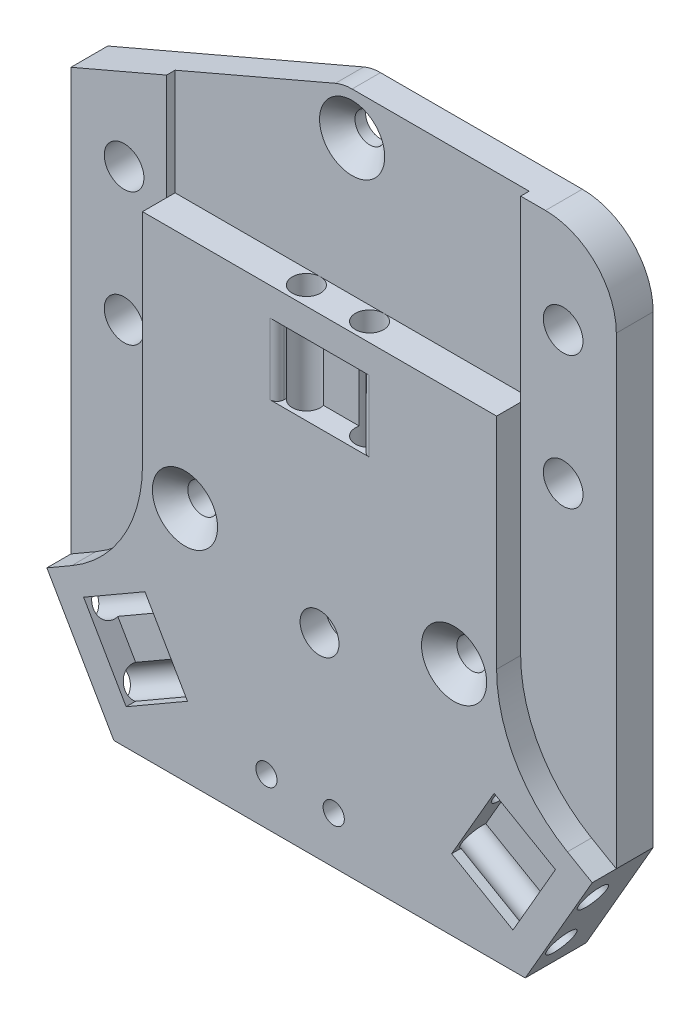
SolidWorks part; units mm, degrees
other "carriage coupler plate"
material "PET"
ref_plane "Front" through (0, 0, 0) normal (0, 0, 1) x (1, 0, 0)
ref_plane "Top" through (0, 0, 0) normal (0, 1, 0) x (1, 0, 0)
ref_plane "Right" through (0, 0, 0) normal (1, 0, 0) x (0, 0, -1)
sketch "Sketch1" plane through (0, 0, 0) normal (0, 0, 1) x (1, 0, 0)
  line L0 (0, 0) -> (0, 30) construction
  line L1 (0, 0) -> (25.9808, -15) construction
  line L2 (0, 0) -> (-25.9808, -15) construction
  dimension "D1" = 120
  dimension "D2" = 120
  dimension "D3" = 30
ref_plane "Plane1" through (0, 30, 0) normal (0, 1, 0) x (1, 0, 0)
sketch "Sketch2" plane through (0, 30, 0) normal (0, 1, 0) x (1, 0, 0)
  line L0 (-4.4589, 0) -> (0, -4.0148) construction
  line L1 (0, 0) -> (-25.9808, 0) construction
  line L2 (0, 0) -> (0, -4.0148) construction
  line L3 (-4.4589, 0) -> (0, 0) construction
  line L4 (0, -5.3962) -> (0, -4.0148) construction
  line L5 (0, -5.3962) -> (-4.4589, 0) construction
  line L7 (-4, -4.0148) -> (4, -4.0148) construction
  line L8 (3.9519, -3.3962) -> (-3.9519, -3.3962) construction
  line L9 (0, -0.3962) -> (0, -3.3962) construction
  line L10 (0, -4.0148) -> (0, -7.3926) construction
  circle A0 centre (-4.4589, 0) radius 2
  circle A1 centre (4.4589, 0) radius 2
  circle A2 centre (0, -4.0148) radius 4
  circle A3 centre (0, -5.3962) radius 5 construction
  circle A4 centre (0, -7.3926) radius 1.5
  dimension "D1" = 4
  dimension "D2" = 8
  dimension "D4" = 10
  dimension "D9" = 3
  dimension "D6" = 7.3926
  dimension "D8" = 8.9177
  dimension "D3" = 42
  dimension "D5" = 50.433
  dimension "D7" = 3.3962
  dimension "D10" = 0.6186
sketch "Sketch3" plane through (0, 0, 0) normal (0, 0, 1) x (1, 0, 0)
  line L0 (0, 30) -> (0, 35) construction
  line L2 (0, 35) -> (0, 39) construction
  line L3 (-25, 39) -> (25, 39)
  line L4 (25, 39) -> (25, -3.5116)
  line L5 (25, -3.5116) -> (38.5044, -11.3084)
  line L6 (0, 0) -> (0, 30) construction
  line L7 (-25, -3.5116) -> (-38.5044, -11.3084)
  line L8 (-25, 39) -> (-25, -3.5116)
  line L9 (4.4589, 30) -> (4.4589, 39) construction
  line L10 (25.9808, -15) -> (33.775, -19.5) construction
  line L11 (29.0456, -27.6916) -> (-29.0456, -27.6916)
  line L13 (0, 0) -> (25.9808, -15) construction
  line L14 (33.775, -19.5) -> (38.5044, -11.3084)
  line L15 (4.4589, 30) -> (0, 30) construction
  line L16 (4.4589, 30) -> (9.4589, 30) construction
  line L17 (-33.775, -19.5) -> (-38.5044, -11.3084)
  line L18 (33.775, -19.5) -> (29.0456, -27.6916)
  line L19 (-33.775, -19.5) -> (-29.0456, -27.6916)
  dimension "D1" = 5
  dimension "D2" = 4
  dimension "D3" = 25
  dimension "D4" = 120
  dimension "D5" = 5
  dimension "D6" = 9.4589
  dimension "D7" = 9.4589
  dimension "D8" = 9
  dimension "D9" = 9
extrude "Boss-Extrude1" add sketch "Sketch3" along normal blind 2.6 and the other way blind 6
fillet "Fillet1" radius 20 2 edges at (-25, -3.5116, -1.7) (25, -3.5116, -1.7)
sketch "Sketch4" plane through (0, 30, 0) normal (0, 1, 0) x (1, 0, 0)
  line L0 (0, -0.0148) -> (0, 0.4852) construction
  line L1 (5.1148, 0.4852) -> (-5.1148, 0.4852)
  line L2 (-5.1148, 0.4852) -> (-6, -0.4)
  line L3 (-6, -0.4) -> (-6, -2.6)
  line L4 (25, -2.6) -> (-25, -2.6) construction
  line L5 (-6, -2.6) -> (6, -2.6)
  line L7 (0, -5.3962) -> (-4.4589, 0) construction
  line L8 (-0.7342, -4.5076) -> (-0.5833, -4.3426)
  line L9 (6, -0.4) -> (6, -2.6)
  line L10 (5.1148, 0.4852) -> (6, -0.4)
  circle A7 centre (0, -4.0148) radius 4 construction
  dimension "D1" = 0.5
  dimension "D2" = 135
  dimension "D3" = 12
  dimension "D4" = 2.2
extrude "Cut-Extrude1" cut sketch "Sketch4" against normal blind 5 and the other way blind 5 contours L5 L9 L10 L1 L2 L3
sketch "Sketch5" plane through (0, 39, 0) normal (0, 1, 0) x (1, 0, 0)
  circle A0 centre (-4.4589, 0) radius 2 construction
  circle A1 centre (4.4589, 0) radius 2 construction
  circle A2 centre (-4.4589, 0) radius 2
  circle A3 centre (4.4589, 0) radius 2
extrude "Cut-Extrude2" cut sketch "Sketch5" against normal blind 20
fillet "Fillet3" radius 1 2 edges at (-6, 30, 2.6) (6, 30, 2.6)
ref_axis "Axis1" through (0, 0, -80.9) along (0, 0, 1)
pattern_circular "CirPattern1" count 3 over 360 about axis through (0, 0, -80.9) along (0, 0, 1) of "Cut-Extrude2", "Cut-Extrude1"
sketch "Sketch6" plane through (0, 0, 2.6) normal (0, 0, 1) x (1, 0, 0)
  circle A0 centre (0, 0) radius 2.75
  dimension "D1" = 5.5
extrude "Cut-Extrude3" cut sketch "Sketch6" against normal through all
sketch "Sketch7" plane through (0, 0, -6) normal (0, 0, -1) x (-1, 0, 0)
  line L2 (0, 0) -> (0, 58.2) construction
  line L3 (-25, 39) -> (25, 39) construction
  line L4 (-25, 39) -> (25, 39)
  line L5 (-25, 39) -> (-25, 54)
  line L6 (-25, 54) -> (-2.3663, 63.7137)
  line L7 (25, 39) -> (25, 54)
  line L8 (25, 54) -> (2.3663, 63.7137)
  arc A0 (2.3663, 63.7137) -> (-2.3663, 63.7137) centre (0, 58.2) ccw
  dimension "D1" = 12
  dimension "D2" = 19.2
  dimension "D3" = 15
extrude "Boss-Extrude2" add sketch "Sketch7" against normal blind 4
sketch "Sketch8" plane through (0, 0, 2.6) normal (0, 0, 1) x (1, 0, 0)
  line L0 (0, 0) -> (0, 58.2) construction
  line L1 (-19, 5.7) -> (19, 5.7) construction
  circle A0 centre (-19, 5.7) radius 2.1
  circle A1 centre (19, 5.7) radius 2.1
  circle A2 centre (0, 58.2) radius 2.1
  arc A3 (2.3663, 63.7137) -> (-2.3663, 63.7137) centre (0, 58.2) ccw construction
  point P10 (0, 5.7)
  dimension "D1" = 4.2
  dimension "D2" = 4.2
  dimension "D3" = 4.2
  dimension "D4" = 52.5
  dimension "D5" = 38
extrude "Cut-Extrude4" cut sketch "Sketch8" against normal through all
chamfer "Chamfer1" distance 2.5 angle 45 3 edges at (-16.9, 5.7, 2.6) (21.1, 5.7, 2.6) (-2.1, 58.2, -2)
sketch "Sketch9" plane through (0, 0, -6) normal (0, 0, -1) x (-1, 0, 0)
  line L0 (0, -27.6916) -> (0, -6.1064) construction
  line L1 (29.0456, -27.6916) -> (-29.0456, -27.6916) construction
  line L2 (-2, -21.0416) -> (7.5, -21.0416) construction
  circle A0 centre (7.5, -21.0416) radius 1.5
  circle A1 centre (-2, -21.0416) radius 1.5
  dimension "D4" = 3
  dimension "D5" = 3
  dimension "D1" = 6.65
  dimension "D2" = 7.5
  dimension "D3" = 9.5
extrude "Cut-Extrude5" cut sketch "Sketch9" against normal through all
sketch "Sketch10" plane through (0, 0, -6) normal (0, 0, -1) x (-1, 0, 0)
  line L0 (25, 54) -> (38.5044, 48.2043)
  line L2 (25, 8.0354) -> (25, 54)
  line L4 (38.5044, -11.3084) -> (38.5044, 48.2043)
  line L7 (38.5044, -11.3084) -> (38.5044, 22.7) construction
  line L8 (35, -9.2851) -> (38.5044, -11.3084)
  line L9 (25, 54) -> (2.3663, 63.7137) construction
  arc A2 (35, -9.2851) -> (25, 8.0354) centre (45, 8.0354) cw
extrude "Boss-Extrude3" add sketch "Sketch10" against normal blind 5.2
sketch "Sketch11" plane through (0, 0, -6) normal (0, 0, -1) x (-1, 0, 0)
  line L0 (-38.5044, -11.3084) -> (-38.5044, 64.2)
  line L2 (-38.5044, -11.3084) -> (-35, -9.2851)
  line L3 (-25, 8.0354) -> (-25, 54)
  line L7 (0, 64.2) -> (-38.5044, 64.2)
  line L8 (-25, 54) -> (-2.3663, 63.7137)
  line L9 (-2.3663, 63.7137) -> (-25, 54) construction
  arc A2 (-35, -9.2851) -> (-25, 8.0354) centre (-45, 8.0354) ccw
  arc A4 (2.3663, 63.7137) -> (-2.3663, 63.7137) centre (0, 58.2) ccw construction
  arc A5 (-2.3663, 63.7137) -> (0, 64.2) centre (0, 58.2) cw
extrude "Boss-Extrude4" add sketch "Sketch11" against normal blind 5.2
sketch "Sketch12" plane through (0, 0, -0.8) normal (0, 0, 1) x (1, 0, 0)
  line L0 (-38.5044, 39.8275) -> (-31, 39.8275) construction
  line L1 (-38.5044, -11.3084) -> (-38.5044, 48.2043) construction
  line L2 (38.5044, 50.8275) -> (31, 50.8275) construction
  line L3 (38.5044, 64.2) -> (38.5044, -11.3084) construction
  line L4 (25, 8.0354) -> (25, 39) construction
  line L5 (-25, 39) -> (-25, 8.0354) construction
  line L6 (25, 39) -> (-25, 39) construction
  line L7 (-31, 39.8275) -> (-31, 21.0775) construction
  line L8 (25, 39) -> (4.4589, 39) construction
  line L9 (31, 50.8275) -> (31, 32.0775) construction
  circle A0 centre (-31, 39.8275) radius 2.8
  circle A1 centre (31, 50.8275) radius 2.8
  circle A2 centre (-31, 21.0775) radius 2.8
  circle A3 centre (31, 32.0775) radius 2.8
  dimension "D5" = 5.6
  dimension "D6" = 5.6
  dimension "D7" = 5.6
  dimension "D9" = 5.6
  dimension "D1" = 0.8275
  dimension "D2" = 11.8275
  dimension "D3" = 6
  dimension "D4" = 6
  dimension "D8" = 18.75
  dimension "D10" = 18.75
fillet "Fillet4" radius 10 1 edges at (38.5044, 64.2, -3.4)
sketch "Sketch13" plane through (0, 0, -6) normal (0, 0, -1) x (-1, 0, 0)
  circle A0 centre (0, 0) radius 7
  dimension "D1" = 14
extrude "Cut-Extrude7" cut sketch "Sketch13" against normal blind 5
sketch "Sketch14" plane through (0, 0, -0.8) normal (0, 0, 1) x (1, 0, 0)
  line L0 (0, 64.2) -> (28.5044, 64.2) construction
  line L1 (-25, 39) -> (25, 39)
  line L2 (-25, 39) -> (-25, 64.2)
  line L3 (-25, 64.2) -> (25, 64.2)
  line L4 (25, 39) -> (25, 64.2)
  line L5 (25, 8.0354) -> (25, 39) construction
extrude "Cut-Extrude8" cut sketch "Sketch14" against normal up to surface (1.2 mm away) up to face at (-4.6, 58.2, -2)
hole_wizard "Ø5.6 (5.6) Diameter Hole1" positions "Sketch15" profile "Sketch16" hole size "Ø5.6" standard "ANSI Metric" end condition through all
sketch "Sketch15" plane through (0, 0, -0.8) normal (0, 0, 1) x (1, 0, 0)
  point P0 (-31, 39.8275)
  point P3 (-31, 21.0775)
  point P6 (31, 32.0775)
  point P9 (31, 50.8275)
sketch "Sketch16" plane through (-31, 39.8275, -0.8) normal (1, 0, 0) x (0, -1, 0)
  line L0 (0, 0) -> (0, 5.2)
  line L1 (0, 5.2) -> (2.8, 5.2)
  line L2 (2.8, 5.2) -> (2.8, 0)
  line L5 (2.8, 0) -> (0, 0)
  line L11 (0, -6.35) -> (0, 107.95) construction
  dimension "Thru Hole Dia." = 5.6
  dimension "Thru Hole Depth" = 5.2
